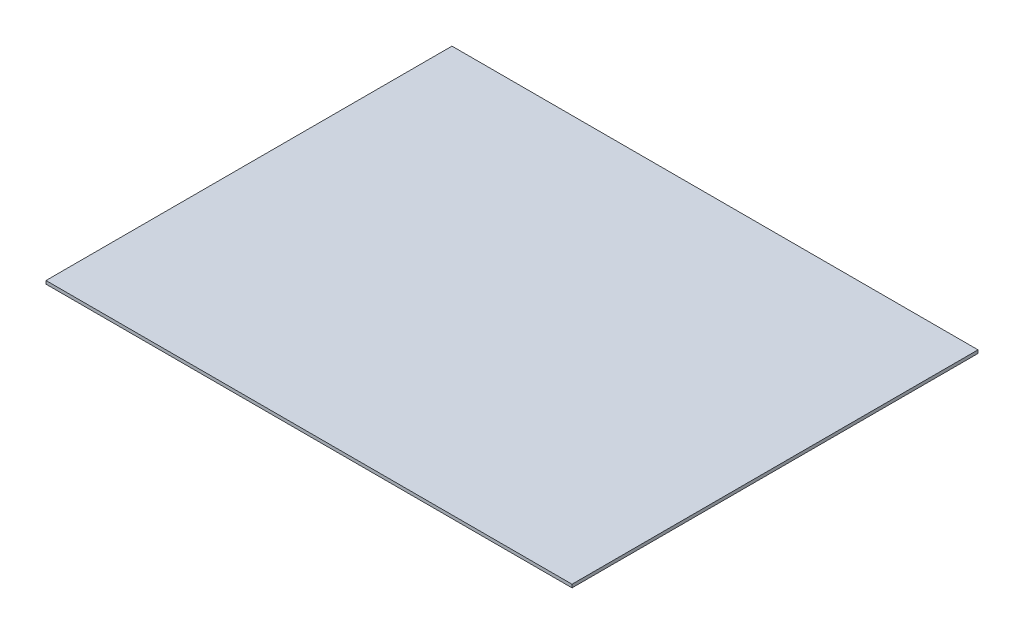
SolidWorks part; units mm, degrees
material "6061-T6 (SS)"
ref_plane "Front" through (0, 0, 0) normal (0, 0, 1) x (1, 0, 0)
ref_plane "Top" through (0, 0, 0) normal (0, 1, 0) x (1, 0, 0)
ref_plane "Right" through (0, 0, 0) normal (1, 0, 0) x (0, 0, -1)
sketch "Sketch1" plane through (0, 0, 0) normal (0, 0, 1) x (1, 0, 0)
  line L0 (-247, 3) -> (247, 3)
  line L1 (-250, 0) -> (250, 0)
  line L2 (-250, 0) -> (-250, 500)
  line L3 (-250, 500) -> (250, 500)
  line L4 (250, 0) -> (250, 500)
  line L5 (247, 3) -> (247, 497)
  line L6 (-247, 497) -> (247, 497)
  line L7 (-247, 3) -> (-247, 497)
  line L8 (-142.1189, 497) -> (-142.1189, 368.6667) construction
  line L9 (-247, 368.6667) -> (247, 368.6667)
  line L10 (-247, 368.6667) -> (-247, 365.6667)
  line L11 (-247, 365.6667) -> (247, 365.6667)
  line L12 (247, 368.6667) -> (247, 365.6667)
  line L13 (-247, 237.3333) -> (247, 237.3333)
  line L14 (-247, 237.3333) -> (-247, 234.3333)
  line L15 (-247, 234.3333) -> (247, 234.3333)
  line L16 (247, 237.3333) -> (247, 234.3333)
  line L17 (-247, 106) -> (247, 106)
  line L18 (-247, 106) -> (-247, 103)
  line L19 (-247, 103) -> (247, 103)
  line L20 (247, 106) -> (247, 103)
  line L21 (-142.1189, 365.6667) -> (-142.1189, 237.3333) construction
  line L22 (-142.1189, 234.3333) -> (-142.1189, 106) construction
  line L23 (-247, 432.8333) -> (-84.3333, 432.8333) construction
  line L24 (-84.3333, 497) -> (-81.3333, 497)
  line L25 (-84.3333, 497) -> (-84.3333, 368.6667)
  line L26 (-84.3333, 368.6667) -> (-81.3333, 368.6667)
  line L27 (-81.3333, 497) -> (-81.3333, 368.6667)
  line L28 (81.3333, 497) -> (84.3333, 497)
  line L29 (81.3333, 497) -> (81.3333, 368.6667)
  line L30 (81.3333, 368.6667) -> (84.3333, 368.6667)
  line L31 (84.3333, 497) -> (84.3333, 368.6667)
  line L32 (-81.3333, 432.8333) -> (81.3333, 432.8333) construction
  line L33 (84.3333, 432.8333) -> (247, 432.8333) construction
  dimension "D1" = 500
  dimension "D2" = 3
  dimension "D3" = 3
  dimension "D4" = 100
  dimension "D5" = 3
  dimension "D6" = 128.3333
  dimension "D7" = 162.6667
extrude "Boss-Extrude1" add sketch "Sketch1" along normal blind 381.25 contours L17 L20 L19 L18
